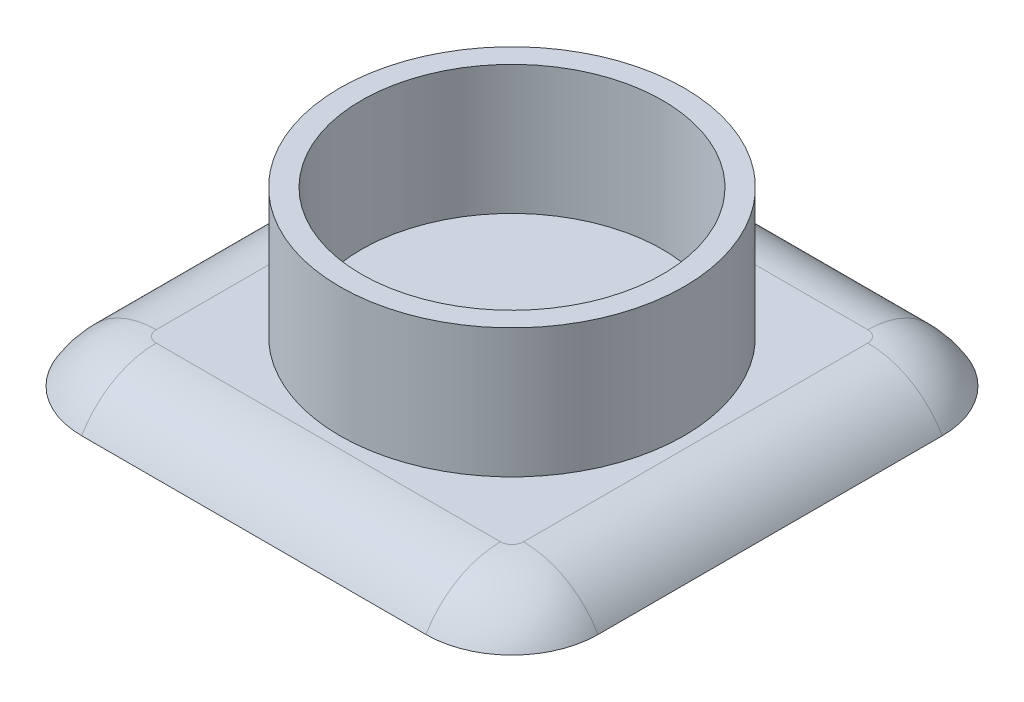
SolidWorks part; units mm, degrees
ref_plane "Front Plane" through (0, 0, 0) normal (0, 0, 1) x (1, 0, 0)
ref_plane "Top Plane" through (0, 0, 0) normal (0, 1, 0) x (1, 0, 0)
ref_plane "Right Plane" through (0, 0, 0) normal (1, 0, 0) x (0, 0, -1)
sketch "Sketch1" plane through (0, 0, 0) normal (0, 1, 0) x (1, 0, 0)
  circle A0 centre (0, 0) radius 4
  circle A1 centre (0, 0) radius 3.5
extrude "Boss-Extrude1" add sketch "Sketch1" along normal blind 3
sketch "Sketch2" plane through (0, 0, 0) normal (0, -1, 0) x (1, 0, 0)
  line L1 (-6, 6) -> (6, 6)
  line L2 (-6, 6) -> (-6, -6)
  line L3 (-6, -6) -> (6, -6)
  line L4 (6, 6) -> (6, -6)
  line L5 (-6, 6) -> (6, -6) construction
  line L6 (-6, -6) -> (6, 6) construction
  point P0 (0, 0)
  dimension "D1" = 12
  dimension "D2" = 12
extrude "Boss-Extrude2" add sketch "Sketch2" along normal blind 1
fillet "Fillet10" radius 2 4 edges at (6, -0.5, 6) (-6, -0.5, 6) (-6, -0.5, -6) (6, -0.5, -6)
fillet "Fillet11" radius 2 8 edges at (-5.4142, 0, 5.4142) (0, 0, 6) (5.4142, 0, 5.4142) (5.4142, 0, -5.4142) (0, 0, -6) (-5.4142, 0, -5.4142) (6, 0, 0) (-6, 0, 0)
